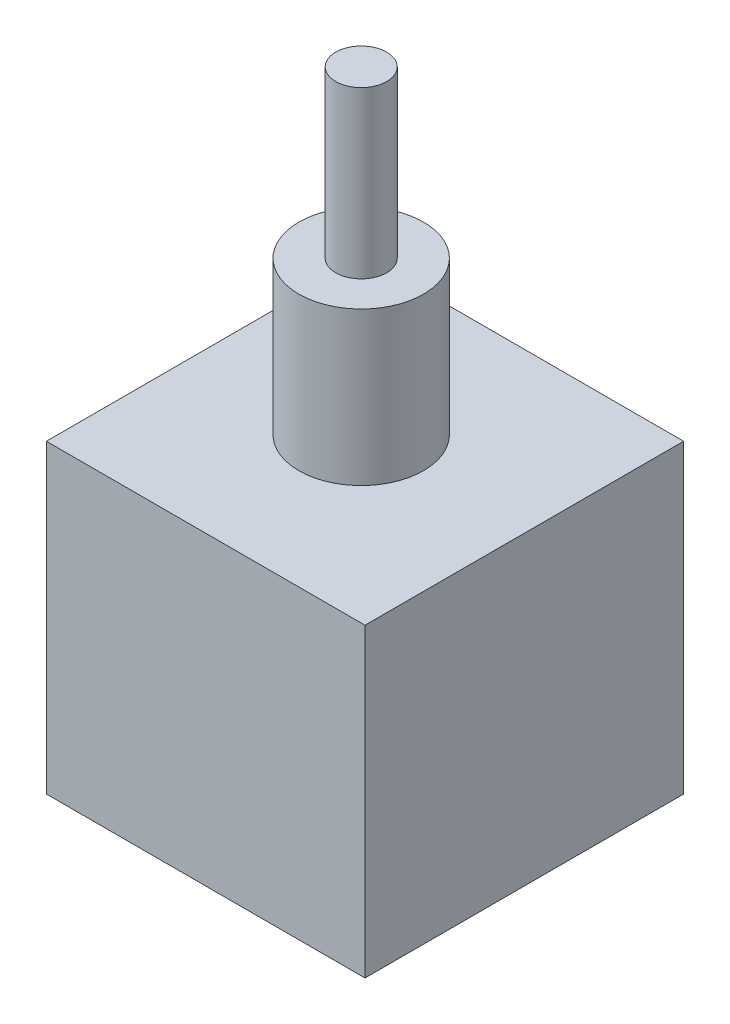
SolidWorks part; units mm, degrees
ref_plane "Спереди" through (0, 0, 0) normal (0, 0, 1) x (1, 0, 0)
ref_plane "Сверху" through (0, 0, 0) normal (0, 1, 0) x (1, 0, 0)
ref_plane "Справа" through (0, 0, 0) normal (1, 0, 0) x (0, 0, -1)
other "Configuration Table"
sketch "Эскиз1" plane through (0, 0, 0) normal (0, 1, 0) x (1, 0, 0)
  line L1 (-14.2865, 14.6433) -> (15.7135, 14.6433)
  line L2 (-14.2865, 14.6433) -> (-14.2865, -15.3567)
  line L3 (-14.2865, -15.3567) -> (15.7135, -15.3567)
  line L4 (15.7135, 14.6433) -> (15.7135, -15.3567)
  dimension "D1" = 30
  dimension "D2" = 30
extrude "высота " add sketch "Эскиз1" along normal blind 28.77
sketch "Эскиз2" plane through (0, 28.77, 0) normal (0, 1, 0) x (1, 0, 0)
  circle A0 centre (0, 0) radius 5.875
  point P3 (0, 0)
  dimension "D1" = 11.75
sketch "Эскиз3" plane through (0, 0, 0) normal (0, 0, 1) x (1, 0, 0)
  line L0 (0, 49.97) -> (0, -1.7648) construction
extrude "Бобышка-Вытянуть2" add sketch "Эскиз2" along normal blind 14.4 contours A0
sketch "Эскиз4" plane through (0, 43.17, 0) normal (0, 1, 0) x (1, 0, 0)
  circle A0 centre (0, 0) radius 2.4
  dimension "D1" = 4.8
extrude "Бобышка-Вытянуть3" add sketch "Эскиз4" along normal blind 15.6
